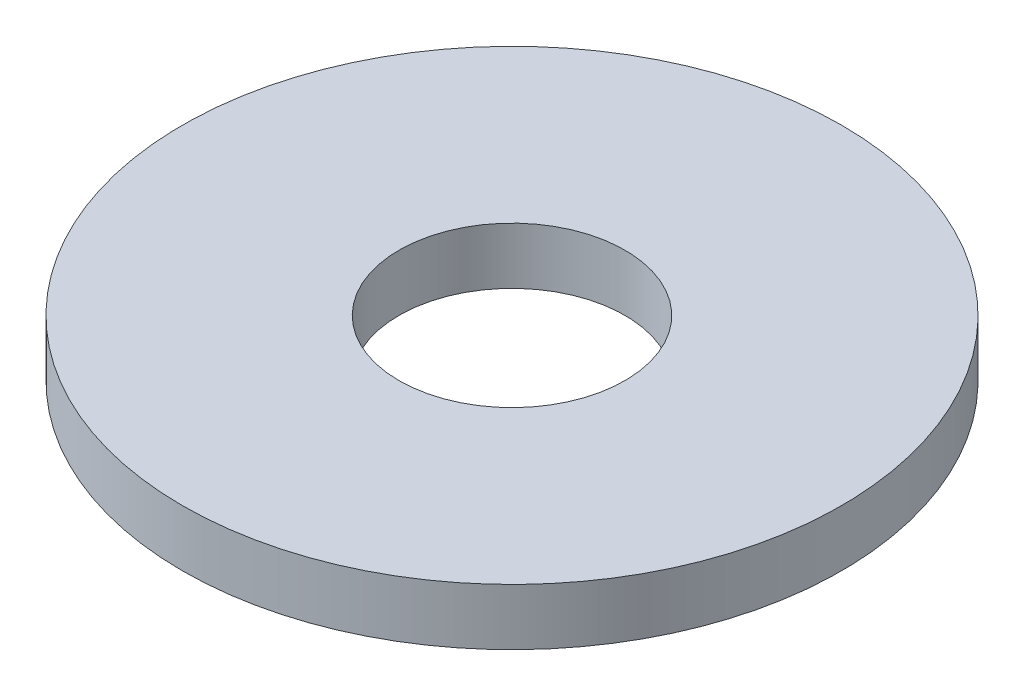
SolidWorks part; units mm, degrees
ref_plane "Front Plane" through (0, 0, 0) normal (0, 0, 1) x (1, 0, 0)
ref_plane "Top Plane" through (0, 0, 0) normal (0, 1, 0) x (1, 0, 0)
ref_plane "Right Plane" through (0, 0, 0) normal (1, 0, 0) x (0, 0, -1)
sketch "Sketch1" plane through (0, 0, 0) normal (0, 1, 0) x (1, 0, 0)
  circle A0 centre (0, 0) radius 87.5
  dimension "FLANGE_OD" = 175
extrude "Boss-Extrude1" add sketch "Sketch1" along normal blind 15
sketch "Sketch2" plane through (0, 0, 0) normal (0, 1, 0) x (1, 0, 0)
  circle A0 centre (0, 0) radius 30
  dimension "BORE_D" = 60
extrude "Cut-Extrude1" cut sketch "Sketch2" along normal through all
sketch "Sketch3" plane through (0, 15, 0) normal (0, 1, 0) x (1, 0, 0)
  circle A0 centre (0, 0) radius 18.4261 construction
  circle A1 centre (-18.4261, 0) radius 3.2326
  dimension "BOLT_D" = 6.4653
  dimension "BOLT_PCD" = 36.8522
extrude "Cut-Extrude2" cut sketch "Sketch3" against normal blind 9.3766 rebuild error yes
pattern_circular "CirPattern1" count 5 over 360 rebuild error yes
